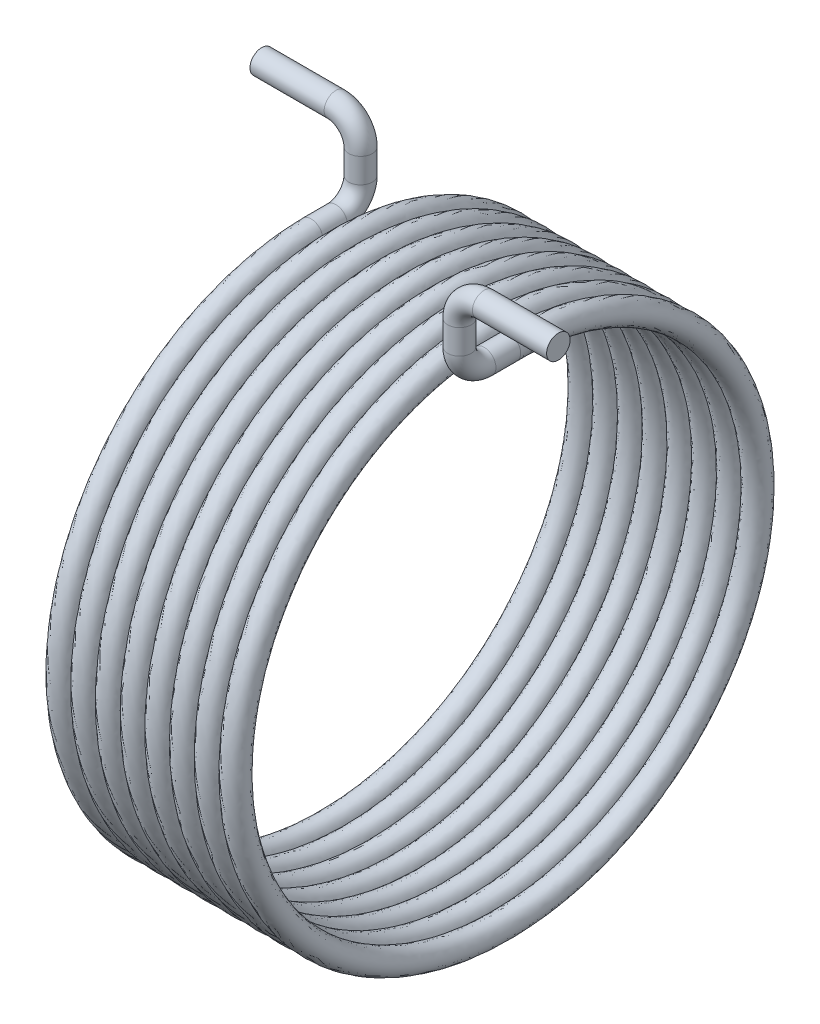
SolidWorks part; units mm, degrees
material "Plain Carbon Steel"
ref_plane "Front Plane" through (0, 0, 0) normal (0, 0, 1) x (1, 0, 0)
ref_plane "Top Plane" through (0, 0, 0) normal (0, 1, 0) x (1, 0, 0)
ref_plane "Right Plane" through (0, 0, 0) normal (1, 0, 0) x (0, 0, -1)
ref_plane "Plane2" through (-2.5, 0, 0) normal (1, 0, 0) x (0, 0, -1)
sketch "Sketch1" plane through (-2.5, 0, 0) normal (1, 0, 0) x (0, 0, -1)
  circle A0 centre (0, 0) radius 10 construction
  circle A1 centre (0.2479, 10.4971) radius 0.5 construction
  circle A2 centre (0, 0) radius 10.5
  dimension "D1" = 20
  dimension "D2" = 1
curve "Helix/Spiral1" pitch 1 height 8 radius 10.5 centre (-2.5, 0, 0) axis (1, 0, 0) start towards (0, 1, 0)
sketch "Sketch2" plane through (0, 0, 0) normal (0, 0, 1) x (1, 0, 0)
  circle A0 centre (-2.4694, 10.3046) radius 0.475
  spline S0 degree 3 poles (-2.5, 10.5) (-2.4793, 10.5) (-2.4374, 9.9533) (-2.375, 7.6179) (-2.3125, 4.1228) (-2.25, 0) (-2.1875, -4.1228) (-2.125, -7.6179) (-2.0625, -9.9533) (-2, -10.7734) (-1.9375, -9.9533) (-1.875, -7.6179) (-1.8125, -4.1228) (-1.75, 0) (-1.6875, 4.1228) (-1.625, 7.6179) (-1.5625, 9.9533) (-1.5, 10.7734) (-1.4375, 9.9533) (-1.375, 7.6179) (-1.3125, 4.1228) (-1.25, 0) (-1.1875, -4.1228) (-1.125, -7.6179) (-1.0625, -9.9533) (-1, -10.7734) (-0.9375, -9.9533) (-0.875, -7.6179) (-0.8125, -4.1228) (-0.75, 0) (-0.6875, 4.1228) (-0.625, 7.6179) (-0.5625, 9.9533) (-0.5, 10.7734) (-0.4375, 9.9533) (-0.375, 7.6179) (-0.3125, 4.1228) (-0.25, 0) (-0.1875, -4.1228) (-0.125, -7.6179) (-0.0625, -9.9533) (0, -10.7734) (0.0625, -9.9533) (0.125, -7.6179) (0.1875, -4.1228) (0.25, 0) (0.3125, 4.1228) (0.375, 7.6179) (0.4375, 9.9533) (0.5, 10.7734) (0.5625, 9.9533) (0.625, 7.6179) (0.6875, 4.1228) (0.75, 0) (0.8125, -4.1228) (0.875, -7.6179) (0.9375, -9.9533) (1, -10.7734) (1.0625, -9.9533) (1.125, -7.6179) (1.1875, -4.1228) (1.25, 0) (1.3125, 4.1228) (1.375, 7.6179) (1.4375, 9.9533) (1.5, 10.7734) (1.5625, 9.9533) (1.625, 7.6179) (1.6875, 4.1228) (1.75, 0) (1.8125, -4.1228) (1.875, -7.6179) (1.9375, -9.9533) (2, -10.7734) (2.0625, -9.9533) (2.125, -7.6179) (2.1875, -4.1228) (2.25, 0) (2.3125, 4.1228) (2.375, 7.6179) (2.4375, 9.9533) (2.5, 10.7734) (2.5625, 9.9533) (2.625, 7.6179) (2.6875, 4.1228) (2.75, 0) (2.8125, -4.1228) (2.875, -7.6179) (2.9375, -9.9533) (3, -10.7734) (3.0625, -9.9533) (3.125, -7.6179) (3.1875, -4.1228) (3.25, 0) (3.3125, 4.1228) (3.375, 7.6179) (3.4375, 9.9533) (3.5, 10.7734) (3.5625, 9.9533) (3.625, 7.6179) (3.6875, 4.1228) (3.75, 0) (3.8125, -4.1228) (3.875, -7.6179) (3.9375, -9.9533) (4, -10.7734) (4.0625, -9.9533) (4.125, -7.6179) (4.1875, -4.1228) (4.25, 0) (4.3125, 4.1228) (4.375, 7.6179) (4.4375, 9.9533) (4.5, 10.7734) (4.5625, 9.9533) (4.625, 7.6179) (4.6875, 4.1228) (4.75, 0) (4.8125, -4.1228) (4.875, -7.6179) (4.9375, -9.9533) (5, -10.7734) (5.0625, -9.9533) (5.125, -7.6179) (5.1875, -4.1228) (5.25, 0) (5.3125, 4.1228) (5.375, 7.6179) (5.4374, 9.9533) (5.4793, 10.5) (5.5, 10.5) knots 0 0 0 0 0.007813 0.015625 0.023438 0.03125 0.039063 0.046875 0.054688 0.0625 0.070313 0.078125 0.085938 0.09375 0.101563 0.109375 0.117188 0.125 0.132813 0.140625 0.148438 0.15625 0.164063 0.171875 0.179688 0.1875 0.195313 0.203125 0.210938 0.21875 0.226563 0.234375 0.242188 0.25 0.257813 0.265625 0.273438 0.28125 0.289063 0.296875 0.304688 0.3125 0.320313 0.328125 0.335938 0.34375 0.351563 0.359375 0.367188 0.375 0.382813 0.390625 0.398438 0.40625 0.414063 0.421875 0.429688 0.4375 0.445313 0.453125 0.460938 0.46875 0.476563 0.484375 0.492188 0.5 0.507813 0.515625 0.523438 0.53125 0.539063 0.546875 0.554688 0.5625 0.570313 0.578125 0.585938 0.59375 0.601563 0.609375 0.617188 0.625 0.632813 0.640625 0.648438 0.65625 0.664063 0.671875 0.679688 0.6875 0.695313 0.703125 0.710938 0.71875 0.726563 0.734375 0.742188 0.75 0.757813 0.765625 0.773438 0.78125 0.789063 0.796875 0.804688 0.8125 0.820313 0.828125 0.835938 0.84375 0.851563 0.859375 0.867188 0.875 0.882813 0.890625 0.898438 0.90625 0.914063 0.921875 0.929688 0.9375 0.945313 0.953125 0.960938 0.96875 0.976563 0.984375 0.992188 1 1 1 1 construction
  dimension "D1" = 0.95
sweep "Sweep1" add profiles "Sketch2" path "Helix/Spiral1"
ref_axis "Axis1" through (-0.7725, 0, 0) along (1, 0, 0)
sketch "Sketch3" plane through (0, 0, 0) normal (0, 0, -1) x (-1, 0, 0)
  circle A0 centre (2.4694, 10.3046) radius 0.475 construction
  circle A2 centre (2.4694, 10.3046) radius 0.475
ref_plane "Plane1" through (-2.4694, 0, 0) normal (1, 0, 0) x (0, 0, -1)
sketch "Sketch5" plane through (0, 0, 0) normal (0, 0, 1) x (1, 0, 0)
  circle A0 centre (5.5306, 10.3046) radius 0.475 construction
  circle A1 centre (5.5306, 10.3046) radius 0.475
sketch3d "3DSketch1"
  line L0 (-2.4694, 10.3046, 0) -> (-2.4694, 10.3046, -1)
  line L1 (-2.4694, 11.3046, -2) -> (-2.4694, 12.3046, -2)
  line L2 (-3.4694, 13.3046, -2) -> (-6.4694, 13.3046, -2)
  arc A0 (-2.4694, 10.3046, -1) -> (-2.4694, 11.3046, -2) centre (-2.4694, 11.3046, -1) ccw
  arc A1 (-2.4694, 12.3046, -2) -> (-3.4694, 13.3046, -2) centre (-3.4694, 12.3046, -2) ccw
  circle A2 centre (-2.4694, 10.3046, 0) radius 0.475 construction
  circle A3 centre (-2.4694, 10.3046, 0) radius 0.475 construction
  point P4 (-1.4694, 11.3046, -1)
  point P8 (-3.4694, 12.3046, -1)
  point P13 (-2.4694, 10.3046, -0.475)
  point P14 (-2.4694, 10.3046, 0.475)
  dimension "D2" = 1
  dimension "D1" = 1
  dimension "D3" = 3
sweep "Sweep4" add profiles "Sketch3" path "3DSketch1"
ref_axis "Axis2" through (-3.4694, 13.3046, -2) along (-1, 0, 0)
sketch3d "3DSketch2"
  line L0 (5.5306, 10.3046, 0) -> (5.5306, 10.3046, 1)
  line L1 (5.5306, 11.3046, 2) -> (5.5306, 12.3046, 2)
  line L2 (6.5306, 13.3046, 2) -> (9.5306, 13.3046, 2)
  arc A0 (5.5306, 10.3046, 1) -> (5.5306, 11.3046, 2) centre (5.5306, 11.3046, 1) ccw
  arc A1 (5.5306, 12.3046, 2) -> (6.5306, 13.3046, 2) centre (6.5306, 12.3046, 2) ccw
  circle A2 centre (5.5306, 10.3046, 0) radius 0.475 construction
  circle A3 centre (5.5306, 10.3046, 0) radius 0.475 construction
  point P3 (4.5306, 11.3046, 1)
  point P7 (6.5306, 12.3046, 1)
  point P12 (5.5306, 10.3046, 0.475)
  point P14 (5.5306, 10.3046, -0.475)
  dimension "D2" = 1
  dimension "D1" = 1
  dimension "D3" = 3
sweep "Sweep5" add profiles "Sketch5" path "3DSketch2"
ref_axis "Axis3" through (2.3138, 13.3046, 2) along (1, 0, 0)
